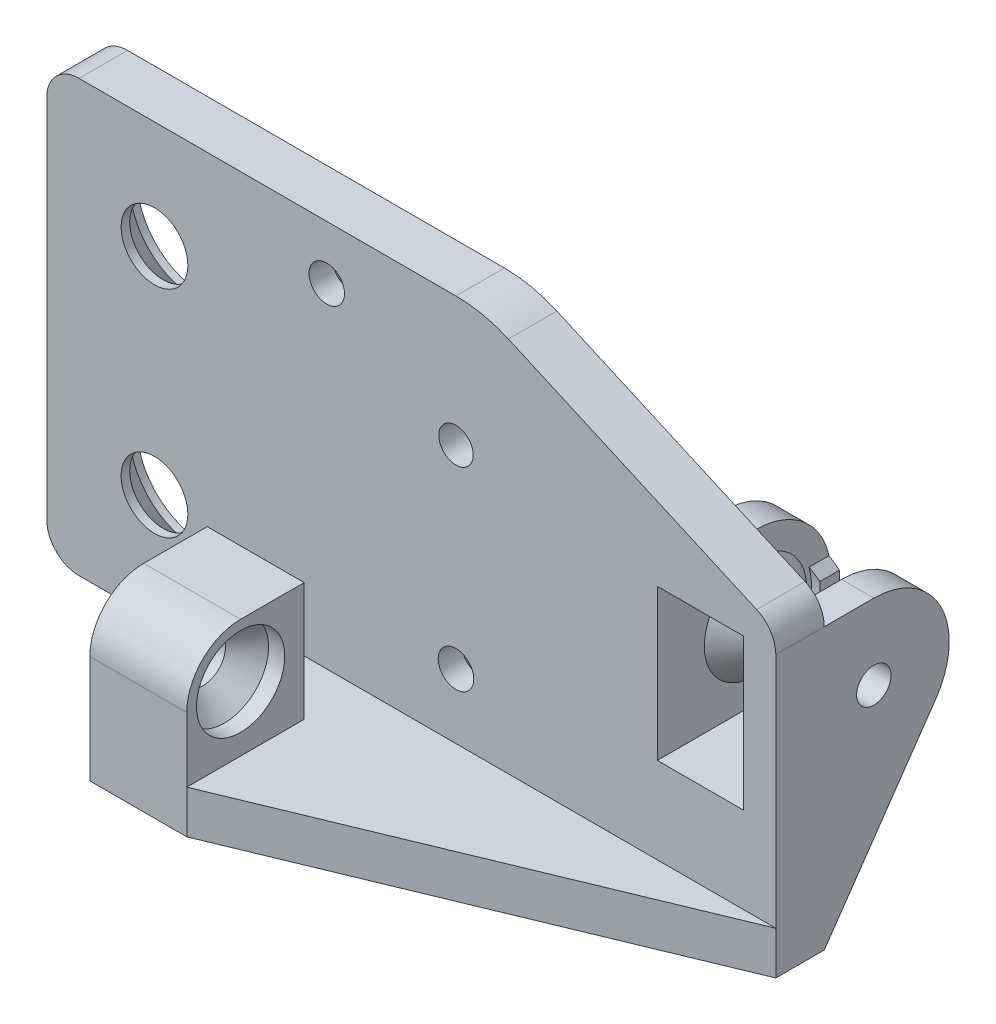
SolidWorks part; units mm, degrees
material "Custom Plastic"
ref_plane "Front Plane" through (0, 0, 0) normal (0, 0, 1) x (1, 0, 0)
ref_plane "Top Plane" through (0, 0, 0) normal (0, 1, 0) x (1, 0, 0)
ref_plane "Right Plane" through (0, 0, 0) normal (1, 0, 0) x (0, 0, -1)
sketch "Sketch1" plane through (0, 0, 0) normal (0, 0, 1) x (1, 0, 0)
  line L0 (-10, -20) -> (-10, 0) construction
  line L1 (-10, -20) -> (10, -20) construction
  line L2 (-10, 0) -> (10, 0) construction
  line L3 (10, -20) -> (10, 0) construction
  line L4 (-10, -20) -> (10, 0) construction
  line L5 (-10, 0) -> (10, -20) construction
  line L6 (-10, 0) -> (-10, 20) construction
  line L7 (-10, 17) -> (-10, -17)
  line L8 (-10, 20) -> (10, 20) construction
  line L9 (10, 0) -> (10, 20) construction
  line L10 (-10, 0) -> (10, 20) construction
  line L11 (-10, 20) -> (10, 0) construction
  line L12 (-7, 20) -> (10, 20)
  line L13 (57.7, 20) -> (57.7, -20)
  line L15 (10, 20) -> (57.7, 20)
  line L18 (57.7, -20) -> (-7, -20)
  circle A0 centre (0, 10) radius 3.1
  circle A1 centre (0, -10) radius 3.1
  arc A2 (-7, 20) -> (-10, 17) centre (-7, 17) ccw
  arc A3 (-10, -17) -> (-7, -20) centre (-7, -17) ccw
  circle A4 centre (28, 8) radius 1.6
  point P0 (0, 10)
  point P1 (0, -10)
  dimension "D2" = 6.2
  dimension "D6" = 3
  dimension "D4" = 3.2
  dimension "D1" = 20
  dimension "D3" = 57.7
  dimension "D5" = 18
  dimension "D7" = 8
extrude "Boss-Extrude1" add sketch "Sketch1" along normal blind 4.5
sketch "Sketch2" plane through (0, -20, 0) normal (0, -1, 0) x (1, 0, 0)
  line L0 (10, 4.5) -> (10, 20.5)
  line L1 (-7, 4.5) -> (57.7, 4.5) construction
  line L2 (10, 20.5) -> (19, 20.5)
  line L3 (19, 20.5) -> (57.7, 4.5)
  line L4 (57.7, 4.5) -> (10, 4.5)
  dimension "D1" = 16
  dimension "D2" = 10
  dimension "D3" = 9
extrude "Boss-Extrude2" add sketch "Sketch2" against normal blind 15
sketch "Sketch3" plane through (57.7, 0, 0) normal (1, 0, 0) x (0, 0, -1)
  line L0 (4.6036, 6) -> (0, 6)
  line L1 (0, -20) -> (0, 20) construction
  line L2 (0, 6) -> (0, -20)
  line L4 (0, -20) -> (10.3655, -4.975)
  arc A0 (10.3655, -4.975) -> (4.6036, 6) centre (4.6036, -1) ccw
  dimension "D1" = 7
  dimension "D2" = 1
extrude "Boss-Extrude3" add sketch "Sketch3" against normal blind 14
sketch "Sketch4" plane through (0, -5, 0) normal (0, 1, 0) x (1, 0, 0)
  line L0 (57.7, -4.5) -> (57.7, 0) construction
  line L1 (10, -4.5) -> (57.7, -4.5)
  line L2 (10, -4.5) -> (10, -9.6)
  line L3 (10, -9.6) -> (19, -9.6)
  line L4 (57.7, -4.5) -> (57.7, -20.5)
  line L5 (19, -20.5) -> (19, -9.6)
  line L6 (19, -20.5) -> (57.7, -20.5)
  dimension "D1" = 5.1
extrude "Cut-Extrude1" cut sketch "Sketch4" against normal offset from surface (11 mm away) 4 contours L6 L4 L1 L2 L3 L5 up to face at (17.9063, -20, 7.8125)
sketch "Sketch5" plane through (57.7, 0, 0) normal (1, 0, 0) x (0, 0, -1)
  circle A0 centre (4.6036, -1) radius 1.6
  dimension "D1" = 3.2
extrude "Cut-Extrude2" cut sketch "Sketch5" against normal through all
sketch "Sketch6" plane through (57.7, 0, 0) normal (1, 0, 0) x (0, 0, -1)
  line L0 (0.7145, 2.8891) -> (8.8191, 10.9937)
  line L1 (8.8191, 10.9937) -> (8.8191, -12.9937)
  line L2 (8.8191, -12.9937) -> (0.7145, -4.8891)
  arc A0 (0.7145, 2.8891) -> (0.7145, -4.8891) centre (4.6036, -1) ccw
  dimension "D1" = 5.5
extrude "Cut-Extrude3" cut sketch "Sketch6" against normal blind 8 from offset 3 offset against normal yes
fillet "Fillet1" radius 5 1 edges at (14.5, -5, 20.5)
sketch "Sketch7" plane through (19, 0, 0) normal (1, 0, 0) x (0, 0, -1)
  line L0 (-4.5, -20) -> (-20.5, -20) construction
  line L1 (-20.5, -10) -> (-20.5, -16) construction
  circle A0 centre (-15.5, -10) radius 2.1
  dimension "D1" = 4.2
  dimension "D2" = 10
  dimension "D3" = 5
extrude "Cut-Extrude4" cut sketch "Sketch7" against normal through all
sketch "Sketch8" plane through (19, 0, 0) normal (1, 0, 0) x (0, 0, -1)
  circle A0 centre (-15.5, -10) radius 4.1
  dimension "D1" = 8.2
extrude "Cut-Extrude5" cut sketch "Sketch8" against normal offset from surface (1.5 mm away) 7.5 up to face at (10, -12.1, 15.5)
chamfer "Chamfer1" distance 2 angle 45 1 edges at (17.5, -12.1, 15.5)
ref_axis "Axis1" through (54.7, -1, -4.6036) along (1, 0, 0)
sketch "Sketch9" plane through (0, 0, 4.5) normal (0, 0, 1) x (1, 0, 0)
  line L0 (46.7, -4.8891) -> (46.7, 2.8891) construction
  line L1 (46.7, 6) -> (54.7, 6)
  line L2 (46.7, 6) -> (46.7, 3.5)
  line L3 (46.7, 3.5) -> (54.7, 3.5) construction
  line L4 (54.7, 6) -> (54.7, 3.5)
  line L5 (54.7, 2.8891) -> (54.7, -4.8891) construction
  line L6 (54.7, -4.8891) -> (54.7, -10.6352) construction
  line L7 (46.7, -5.5) -> (54.7, -5.5) construction
  line L8 (46.7, -5.5) -> (46.7, -8)
  line L9 (46.7, -8) -> (54.7, -8)
  line L10 (54.7, -5.5) -> (54.7, -8)
  line L11 (54.7, 3.5) -> (54.7, -5.5)
  line L12 (54.7, -1) -> (57.7, -1) construction
  line L13 (46.7, 3.5) -> (46.7, -5.5)
  point P14 (54.7, -1)
  dimension "D1" = 2.5
  dimension "D2" = 9
extrude "Cut-Extrude6" cut sketch "Sketch9" against normal through all
sketch "Sketch10" plane through (0, 0, 0) normal (0, 0, -1) x (-1, 0, 0)
  line L1 (-57.7, 6) -> (-57.7, 20)
  line L2 (-57.7, 20) -> (-28, 20)
  line L3 (-55.9166, 8.7422) -> (-32.8666, 18.9689)
  arc A0 (-28, 20) -> (-32.8666, 18.9689) centre (-28, 8) ccw
  arc A1 (-55.9166, 8.7422) -> (-57.7, 6) centre (-54.7, 6) ccw
extrude "Cut-Extrude7" cut sketch "Sketch10" against normal through all
sketch "Sketch11" plane through (0, 0, 0) normal (0, 0, -1) x (-1, 0, 0)
  line L1 (-30.75, -8.4123) -> (-30.75, -11.5877) construction
  line L2 (-30.75, -11.5877) -> (-28, -13.1754) construction
  line L3 (-28, -13.1754) -> (-25.25, -11.5877) construction
  line L4 (-25.25, -11.5877) -> (-25.25, -8.4123) construction
  line L5 (-25.25, -8.4123) -> (-28, -6.8246) construction
  line L6 (-28, -6.8246) -> (-30.75, -8.4123) construction
  line L7 (-13.25, 13.4123) -> (-13.25, 16.5877) construction
  line L8 (-13.25, 16.5877) -> (-16, 18.1754) construction
  line L9 (-16, 18.1754) -> (-18.75, 16.5877) construction
  line L10 (-18.75, 16.5877) -> (-18.75, 13.4123) construction
  line L11 (-18.75, 13.4123) -> (-16, 11.8246) construction
  line L12 (-16, 11.8246) -> (-13.25, 13.4123) construction
  circle A0 centre (-16, 15) radius 1.65
  circle A1 centre (-28, -10) radius 1.65
  circle A2 centre (-28, -10) radius 2.75 construction
  circle A3 centre (-16, 15) radius 2.75 construction
  circle A4 centre (-28, 8) radius 1.6 construction
  point P20 (-28, 8)
  dimension "D1" = 3.3
  dimension "D2" = 5.5
  dimension "D6" = 10
  dimension "D3" = 12
  dimension "D4" = 15
extrude "Cut-Extrude9" cut sketch "Sketch11" against normal through all
sketch "Sketch13" plane through (46.7, 0, 0) normal (1, 0, 0) x (0, 0, -1)
  circle A0 centre (4.6036, -1) radius 2.75
  circle A1 centre (4.6036, -1) radius 1.6
  circle A4 centre (4.6036, -1) radius 1.6 construction
  point P9 (4.6036, -2.5)
  point P11 (10.6036, -2.5)
  point P12 (4.6036, 0.5)
  point P13 (10.6036, 0.5)
  dimension "D1" = 5.5
extrude "Boss-Extrude4" add sketch "Sketch13" along normal blind 2
sketch "Sketch15" plane through (46.7, 0, 0) normal (1, 0, 0) x (0, 0, -1)
  line L1 (9.5826, 0.5) -> (11.441, 0.5)
  line L3 (9.5826, -2.5) -> (11.441, -2.5)
  arc A0 (9.5826, -2.5) -> (9.5826, 0.5) centre (4.6036, -1) ccw
  arc A1 (11.441, -2.5) -> (11.441, 0.5) centre (4.6036, -1) ccw
  arc A2 (10.3655, -4.975) -> (4.6036, 6) centre (4.6036, -1) ccw construction
  dimension "D1" = 5.2
  dimension "D2" = 3
extrude "Boss-Extrude5" add sketch "Sketch15" along normal blind 0.825
ref_plane "Plane1" through (50.7, 0, 0) normal (1, 0, 0) x (0, 0, -1)
mirror "Mirror1" about plane through (50.7, 0, 0) normal (1, 0, 0) of "Boss-Extrude5", "Boss-Extrude4"
chamfer "Chamfer3" distance 2 angle 45 2 edges at (54.7, 1.75, -4.6036) (46.7, 1.75, -4.6036)
sketch "Sketch14" plane through (0, 0, 0) normal (0, 0, -1) x (-1, 0, 0)
  circle A0 centre (0, -10) radius 6.1
  circle A1 centre (0, 10) radius 6.1
  dimension "D1" = 12.2
extrude "Cut-Extrude10" cut sketch "Sketch14" against normal blind 0.7
chamfer "Chamfer4" distance 3 angle 45 2 edges at (-3.1, -10, 0.7) (-3.1, 10, 0.7)
chamfer "Chamfer5" distance 0.83 angle 45 4 edges at (53.875, -2.5, -10.5118) (53.875, 0.5, -10.5118) (47.525, -2.5, -10.5118) (47.525, 0.5, -10.5118)
sketch "Sketch16" plane through (0, 0, 0) normal (0, 0, -1) x (-1, 0, 0)
  circle A0 centre (-28, -10) radius 3.4
  circle A1 centre (-16, 15) radius 3.4
  dimension "D1" = 6.8
extrude "Cut-Extrude11" cut sketch "Sketch16" against normal blind 0.5
chamfer "Chamfer6" distance 1.8 angle 45 2 edges at (26.35, -10, 0.5) (14.35, 15, 0.5)
sketch "Sketch17" plane through (10, 0, 0) normal (-1, 0, 0) x (0, 0, 1)
  line L0 (15.5, -10) -> (16.9849, -8.5151)
  line L1 (16.9849, -8.5151) -> (15.9498, -7.48)
  line L2 (15.9498, -7.48) -> (15.0502, -7.48)
  line L3 (15.0502, -7.48) -> (14.0151, -8.5151)
  line L4 (14.0151, -8.5151) -> (15.5, -10)
  circle A0 centre (15.5, -10) radius 2.1 construction
  point P0 (15.5, -7.9)
  dimension "D1" = 0.42
extrude "Cut-Extrude12" cut sketch "Sketch17" against normal through all
equation "\"y-cross-rib-thickness\"=4"
equation "\"y-rib-thickness\"=6"
equation "\"bed-plate-thickness\"=3"
equation "\"x-plate-thickness\"=5"
equation "\"rod-diameter\"=12"
equation "\"t-nut-hole-diameter\"=3"
equation "\"y-plate-thickness\"=5"
equation "\"D1@Sketch4\"=\"y-plate-thickness\"+.1"
equation "\"D1@Boss-Extrude5\"=(8-6.35)/2"
